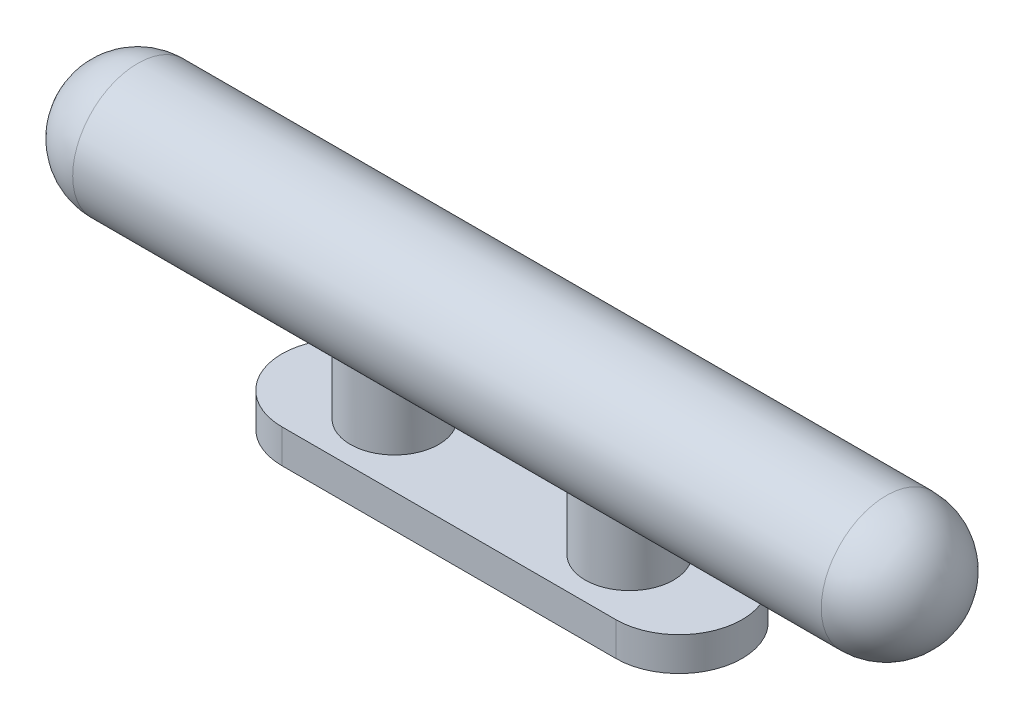
SolidWorks part; units mm, degrees
material "6061-T6 (SS)"
ref_plane "Front Plane" through (0, 0, 0) normal (0, 0, 1) x (1, 0, 0)
ref_plane "Top Plane" through (0, 0, 0) normal (0, 1, 0) x (1, 0, 0)
ref_plane "Right Plane" through (0, 0, 0) normal (1, 0, 0) x (0, 0, -1)
sketch "Sketch1" plane through (0, 0, 0) normal (0, 1, 0) x (1, 0, 0)
  line L0 (0, 0) -> (57.9374, 0) construction
  line L1 (0, 10.9537) -> (57.9374, 10.9537)
  line L2 (0, -10.9537) -> (57.9374, -10.9537)
  arc A0 (0, 10.9537) -> (0, -10.9537) centre (0, 0) ccw
  arc A1 (57.9374, -10.9537) -> (57.9374, 10.9537) centre (57.9374, 0) ccw
  point P3 (28.9687, 0)
  point P8 (-10.9537, 0)
  point P9 (68.8912, 0)
  dimension "D1" = 79.8449
  dimension "D2" = 21.9075
extrude "Boss-Extrude1" add sketch "Sketch1" along normal blind 5.842
sketch "Sketch2" plane through (0, 5.842, 0) normal (0, 1, 0) x (1, 0, 0)
  line L0 (8.5979, 0) -> (49.3395, 0) construction
  line L1 (57.9374, 10.9537) -> (0, 10.9537) construction
  circle A0 centre (8.5979, 0) radius 7.6708
  circle A1 centre (49.3395, 0) radius 7.6708
  point P4 (28.9687, 0)
  point P7 (28.9687, 10.9537)
  dimension "D1" = 15.3416
  dimension "D2" = 15.3416
  dimension "D3" = 40.7416
extrude "Boss-Extrude2" add sketch "Sketch2" along normal blind 14.224
ref_plane "Plane1" through (0, 25.7048, 0) normal (0, 1, 0) x (1, 0, 0)
sketch "Sketch3" plane through (0, 25.7048, 0) normal (0, 1, 0) x (1, 0, 0)
  line L0 (-35.9537, 0) -> (93.8911, 0) construction
  line L2 (-35.9537, -11.2776) -> (93.8911, -11.2776)
  line L3 (57.9374, 10.9537) -> (0, 10.9537) construction
  line L4 (0, -10.9537) -> (57.9374, -10.9537) construction
  line L5 (105.1687, 0) -> (-47.2313, 0)
  arc A0 (-47.2313, 0) -> (-35.9537, -11.2776) centre (-35.9537, 0) ccw
  arc A1 (93.8911, -11.2776) -> (105.1687, 0) centre (93.8911, 0) ccw
  point P3 (28.9687, 0)
  point P13 (28.9687, -10.9537)
ref_axis "Axis1" through (-40.3982, 25.7048, 0) along (-1, 0, 0)
revolve "Revolve6" add sketch "Sketch3" angle 360 about L0
